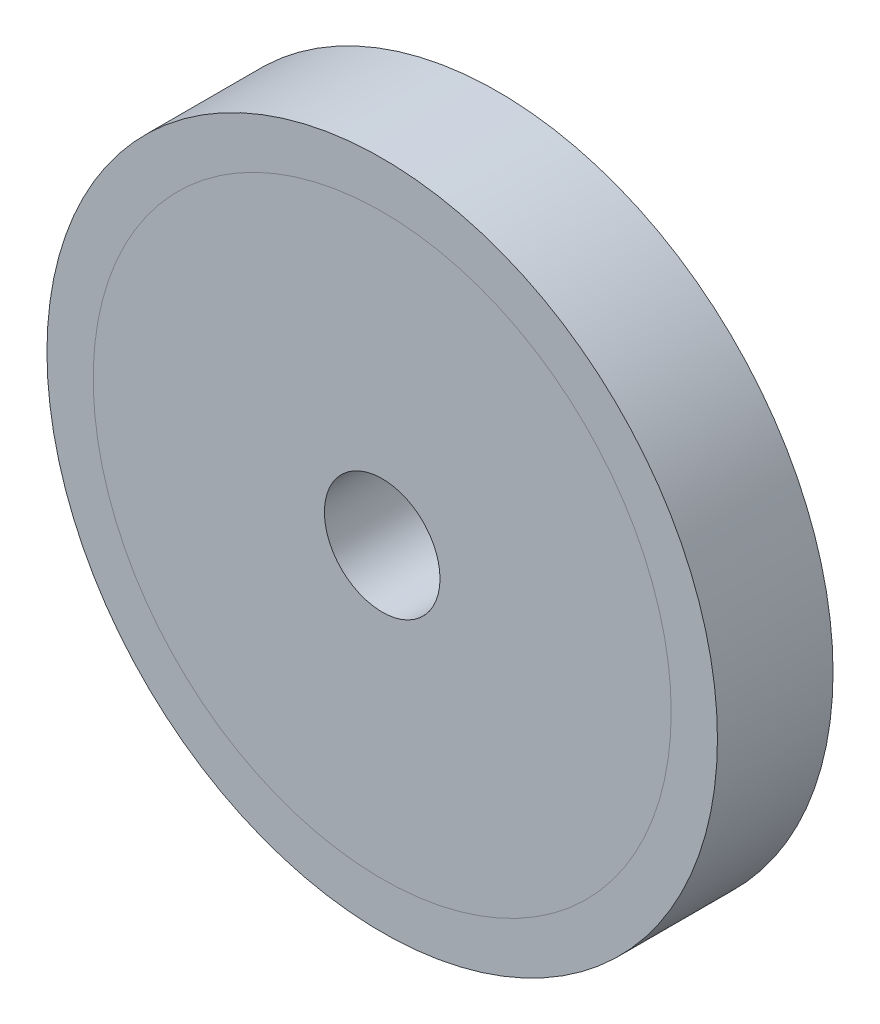
SolidWorks part; units mm, degrees
other "Solid core"
other "Rubber"
ref_plane "Front" through (0, 0, 0) normal (0, 0, 1) x (1, 0, 0)
ref_plane "Top" through (0, 0, 0) normal (0, 1, 0) x (1, 0, 0)
ref_plane "Right" through (0, 0, 0) normal (1, 0, 0) x (0, 0, -1)
sketch "Sketch1" plane through (0, 0, 0) normal (0, 0, 1) x (1, 0, 0)
  circle A0 centre (0, 0) radius 5
  circle A1 centre (0, 0) radius 5.8
  dimension "D1" = 10
  dimension "D2" = 0.8
extrude "Boss-Extrude1" add sketch "Sketch1" along normal blind 2
extrude "Boss-Extrude2" add sketch "Sketch1<2>" along normal blind 2 separate body contours A0 region at (0, 0, 0)
sketch "Sketch1<2>" plane through (0, 0, 0) normal (0, 0, 1) x (1, 0, 0) same geometry as "Sketch1"
sketch "Sketch2" plane through (0, 0, 2) normal (0, 0, 1) x (1, 0, 0)
  circle A0 centre (0, 0) radius 1
  dimension "D1" = 2
extrude "Cut-Extrude1" cut sketch "Sketch2" against normal blind 2
